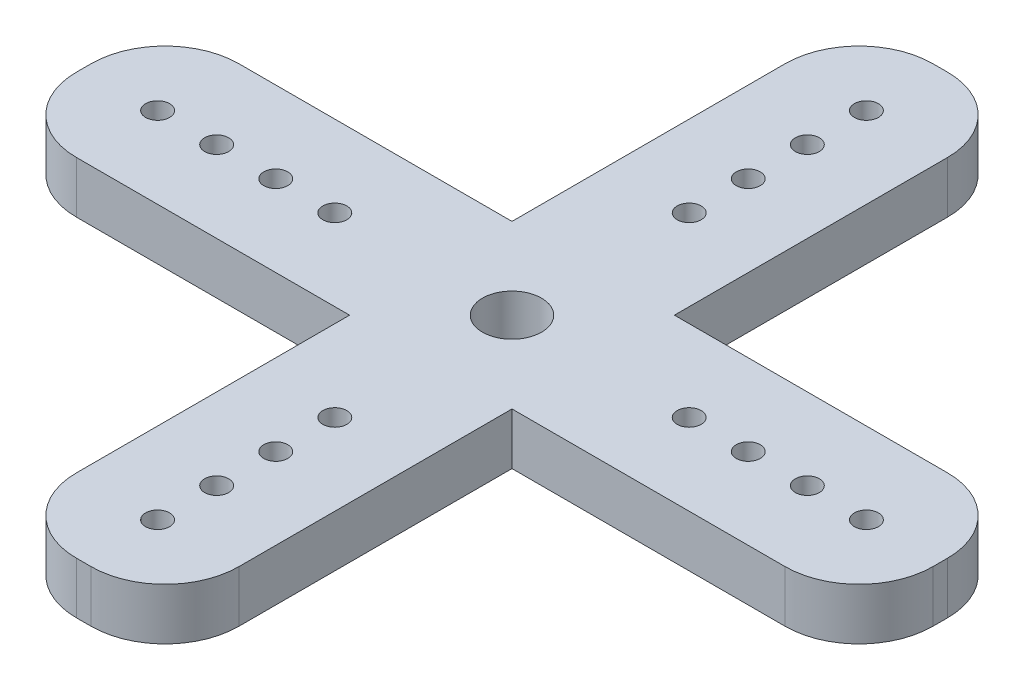
SolidWorks part; units mm, degrees
ref_plane "Front Plane" through (0, 0, 0) normal (0, 0, 1) x (1, 0, 0)
ref_plane "Top Plane" through (0, 0, 0) normal (0, 1, 0) x (1, 0, 0)
ref_plane "Right Plane" through (0, 0, 0) normal (1, 0, 0) x (0, 0, -1)
sketch "Sketch1" plane through (0, 0, 0) normal (0, 1, 0) x (1, 0, 0)
  line L0 (0, -1000) -> (0, 49000) construction
  line L1 (-2.75, 14.5) -> (2.75, 14.5)
  line L2 (-2.75, 14.5) -> (-2.75, 0)
  line L3 (-2.75, 0) -> (2.75, 0)
  line L4 (2.75, 14.5) -> (2.75, 0)
  circle A0 centre (0, 12) radius 0.4064
  circle A1 centre (0, 10) radius 0.4064
  circle A2 centre (0, 8) radius 0.4064
  circle A3 centre (0, 6) radius 0.4064
  point P4 (0, 0)
  dimension "D3" = 0.8128
  dimension "D1" = 5.5
  dimension "D2" = 14.5
  dimension "D4" = 12
  dimension "D5" = 4
extrude "Boss-Extrude1" add sketch "Sketch1" along normal blind 1.75
fillet "Fillet1" radius 2.5 2 edges at (-2.75, 0.875, -14.5) (2.75, 0.875, -14.5)
ref_axis "Axis1" through (0, 0, 0) along (0, 1, 0)
pattern_circular "CirPattern1" count 4 over 360 about axis through (0, 0, 0) along (0, 1, 0) of "Boss-Extrude1", "Fillet1"
sketch "Sketch2" plane through (0, 1.75, 0) normal (0, 1, 0) x (1, 0, 0)
  circle A0 centre (0, 0) radius 1
extrude "Cut-Extrude1" cut sketch "Sketch2" against normal up to next
